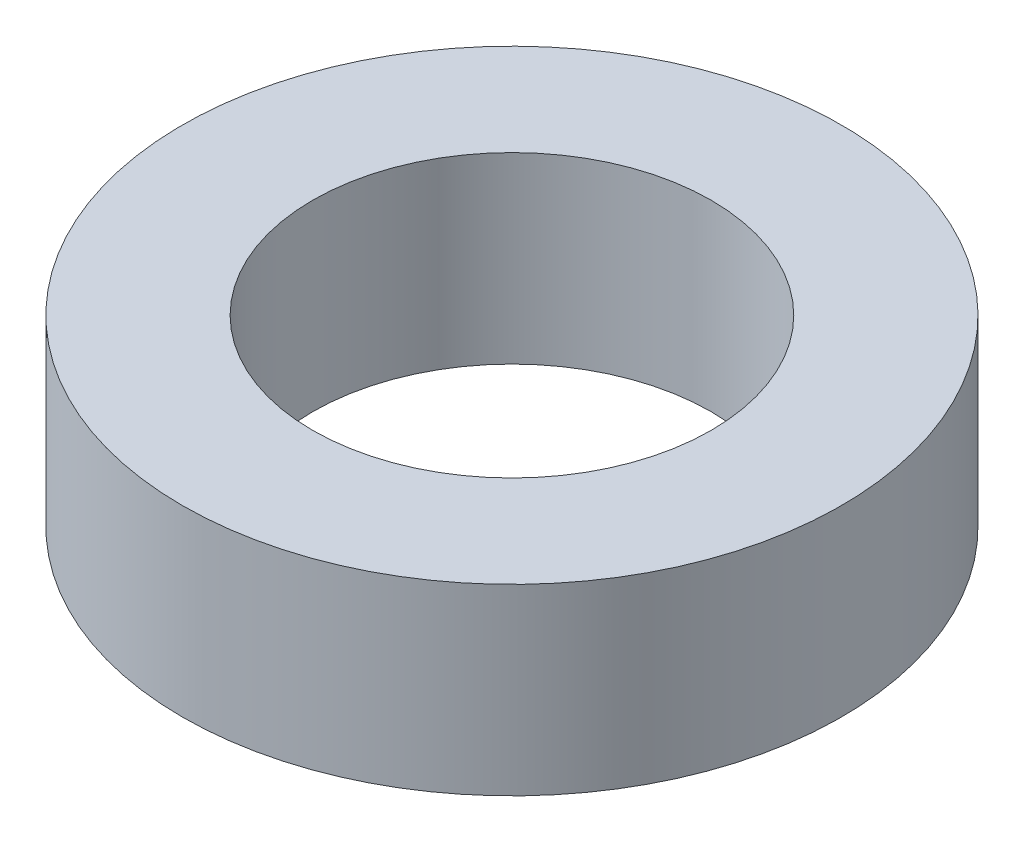
SolidWorks part; units mm, degrees
ref_plane "Front Plane" through (0, 0, 0) normal (0, 0, 1) x (1, 0, 0)
ref_plane "Top Plane" through (0, 0, 0) normal (0, 1, 0) x (1, 0, 0)
ref_plane "Right Plane" through (0, 0, 0) normal (1, 0, 0) x (0, 0, -1)
sketch "Sketch1" plane through (0, 0, 0) normal (0, 1, 0) x (1, 0, 0)
  circle A0 centre (0, 0) radius 3.2639
  circle A1 centre (0, 0) radius 5.3975
  dimension "D1" = 6.5278
  dimension "D2" = 10.795
extrude "Boss-Extrude1" add sketch "Sketch1" along normal blind 3
